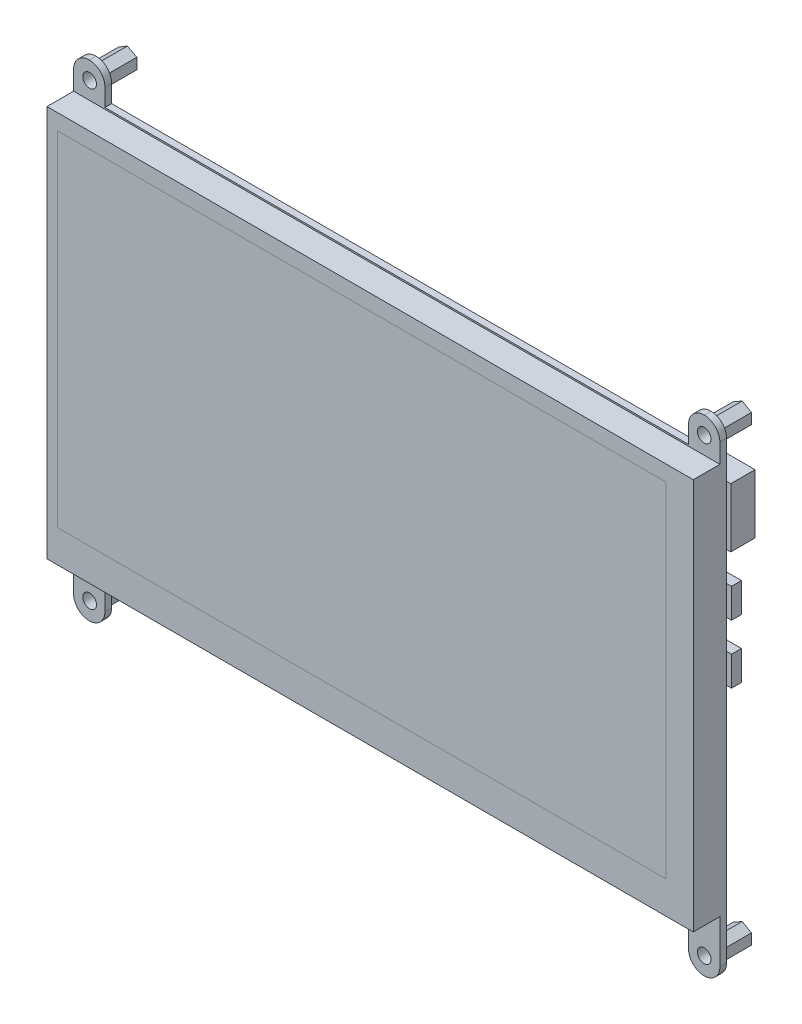
SolidWorks part; units mm, degrees
ref_plane "Plan de face" through (0, 0, 0) normal (0, 0, 1) x (1, 0, 0)
ref_plane "Plan de dessus" through (0, 0, 0) normal (0, 1, 0) x (1, 0, 0)
ref_plane "Plan de droite" through (0, 0, 0) normal (1, 0, 0) x (0, 0, -1)
sketch "Esquisse1" plane through (0, 0, 0) normal (0, 0, 1) x (1, 0, 0)
  line L0 (-74.5, 53.5) -> (74.5, 53.5)
  line L1 (-82.5, 62) -> (-82.5, -62)
  line L2 (-74.5, -53.5) -> (74.5, -53.5)
  line L3 (82.5, 62) -> (82.5, -62)
  line L4 (82.5, -62) -> (74.5, -62)
  line L5 (74.5, -62) -> (74.5, -53.5)
  line L6 (-74.5, -53.5) -> (-74.5, -62)
  line L7 (-74.5, -62) -> (-82.5, -62)
  line L8 (82.5, 62) -> (74.5, 62)
  line L9 (74.5, 62) -> (74.5, 53.5)
  line L10 (-74.5, 53.5) -> (-74.5, 62)
  line L11 (-74.5, 62) -> (-82.5, 62)
  line L12 (78.5, -57.54) -> (78.5, 57.54) construction
  line L13 (78.5, 57.54) -> (-78.4, 57.54) construction
  circle A0 centre (78.5, 57.54) radius 1.75
  circle A1 centre (-78.4, 57.54) radius 1.75
  circle A2 centre (-78.4, -57.54) radius 1.75
  circle A3 centre (78.5, -57.54) radius 1.75
  point P3 (78.5, 0)
  point P21 (78.5, -62)
  point P22 (82.5, 0)
  point P28 (0, 53.5)
  point P29 (-82.5, 0)
  dimension "D1" = 3.5
  dimension "D2" = 165
  dimension "D3" = 107
  dimension "D4" = 8.5
  dimension "D5" = 8
  dimension "D6" = 156.9
  dimension "D7" = 115.08
extrude "Boss.-Extru.1" add sketch "Esquisse1" along normal blind 1.72
fillet "Congé1" radius 4 8 edges at (74.5, -62, 0.86) (82.5, -62, 0.86) (82.5, 62, 0.86) (74.5, 62, 0.86) (-74.5, 62, 0.86) (-82.5, 62, 0.86) (-82.5, -62, 0.86) (-74.5, -62, 0.86)
sketch "Esquisse2" plane through (0, 0, 1.72) normal (0, 0, 1) x (1, 0, 0)
  line L0 (-82.5, 58) -> (-82.5, -58) construction
  line L1 (-82.5, -46.9) -> (82.5, -46.9)
  line L2 (-82.5, -46.9) -> (-82.5, 53.1)
  line L3 (-82.5, 53.1) -> (82.5, 53.1)
  line L4 (82.5, -46.9) -> (82.5, 53.1)
  line L5 (82.5, -58) -> (82.5, 58) construction
  line L6 (74.5, 53.5) -> (-74.5, 53.5) construction
  dimension "D1" = 0.4
  dimension "D2" = 100
extrude "Boss.-Extru.2" add sketch "Esquisse2" along normal blind 6.79
sketch "Esquisse3" plane through (0, 0, 0) normal (0, 0, -1) x (-1, 0, 0)
  line L0 (-74.5, 53.5) -> (74.5, 53.5) construction
  line L1 (-83.57, 33.4) -> (-71.4, 33.4)
  line L2 (-83.57, 33.4) -> (-83.57, 48.5)
  line L3 (-83.57, 48.5) -> (-71.4, 48.5)
  line L4 (-71.4, 33.4) -> (-71.4, 48.5)
  line L5 (-82.5, -58) -> (-82.5, 58) construction
  dimension "D1" = 5
  dimension "D2" = 12.17
  dimension "D3" = 15.1
  dimension "D4" = 1.07
extrude "Boss.-Extru.3" add sketch "Esquisse3" along normal blind 6.19
sketch "Esquisse4" plane through (0, 0, 0) normal (0, 0, -1) x (-1, 0, 0)
  line L0 (-82.5, -58) -> (-82.5, 33.4) construction
  line L1 (-83.75, 18.38) -> (-77.9, 18.38)
  line L2 (-83.75, 18.38) -> (-83.75, 25.9)
  line L3 (-83.75, 25.9) -> (-77.9, 25.9)
  line L4 (-77.9, 18.38) -> (-77.9, 25.9)
  line L5 (-83.75, 3.36) -> (-77.9, 3.36)
  line L6 (-83.75, 3.36) -> (-83.75, 10.88)
  line L7 (-83.75, 10.88) -> (-77.9, 10.88)
  line L8 (-77.9, 3.36) -> (-77.9, 10.88)
  line L9 (-82.5, 33.4) -> (-71.4, 33.4) construction
  dimension "D1" = 7.52
  dimension "D2" = 1.25
  dimension "D3" = 5.85
  dimension "D4" = 7.5
  dimension "D5" = 7.5
extrude "Boss.-Extru.4" add sketch "Esquisse4" along normal blind 2.55
sketch "Esquisse5" plane through (0, 0, 0) normal (0, 0, -1) x (-1, 0, 0)
  line L1 (-78.5, -54.8265) -> (-80.85, -56.1832)
  line L2 (-80.85, -56.1832) -> (-80.85, -58.8968)
  line L3 (-80.85, -58.8968) -> (-78.5, -60.2535)
  line L4 (-78.5, -60.2535) -> (-76.15, -58.8968)
  line L5 (-76.15, -58.8968) -> (-76.15, -56.1832)
  line L6 (-76.15, -56.1832) -> (-78.5, -54.8265)
  line L7 (-78.5, 60.2535) -> (-80.85, 58.8968)
  line L8 (-80.85, 58.8968) -> (-80.85, 56.1832)
  line L9 (-80.85, 56.1832) -> (-78.5, 54.8265)
  line L10 (-78.5, 54.8265) -> (-76.15, 56.1832)
  line L11 (-76.15, 56.1832) -> (-76.15, 58.8968)
  line L12 (-76.15, 58.8968) -> (-78.5, 60.2535)
  line L13 (78.4608, 60.2529) -> (76.081, 58.9491)
  line L14 (76.081, 58.9491) -> (76.0202, 56.2362)
  line L15 (76.0202, 56.2362) -> (78.3392, 54.8271)
  line L16 (78.3392, 54.8271) -> (80.719, 56.1309)
  line L17 (80.719, 56.1309) -> (80.7798, 58.8438)
  line L18 (80.7798, 58.8438) -> (78.4608, 60.2529)
  line L19 (78.4, -54.8265) -> (76.05, -56.1832)
  line L20 (76.05, -56.1832) -> (76.05, -58.8968)
  line L21 (76.05, -58.8968) -> (78.4, -60.2535)
  line L22 (78.4, -60.2535) -> (80.75, -58.8968)
  line L23 (80.75, -58.8968) -> (80.75, -56.1832)
  line L24 (80.75, -56.1832) -> (78.4, -54.8265)
  circle A0 centre (-78.5, -57.54) radius 2.35 construction
  circle A1 centre (-78.5, 57.54) radius 2.35 construction
  circle A2 centre (78.4, 57.54) radius 2.35 construction
  circle A3 centre (78.4, -57.54) radius 2.35 construction
  circle A4 centre (-78.5, 57.54) radius 1.75 construction
  circle A5 centre (-78.5, -57.54) radius 1.75 construction
  circle A6 centre (78.4, -57.54) radius 1.75 construction
  circle A7 centre (78.4, 57.54) radius 1.75 construction
  circle A8 centre (-78.5, 57.54) radius 1.75
  circle A9 centre (-78.5, -57.54) radius 1.75
  circle A10 centre (78.4, -57.54) radius 1.75
  circle A11 centre (78.4, 57.54) radius 1.75
  dimension "D1" = 4.7
extrude "Boss.-Extru.5" add sketch "Esquisse5" along normal blind 8
sketch "Esquisse6" plane through (0, 0, 8.51) normal (0, 0, 1) x (1, 0, 0)
  line L0 (82.5, 53.1) -> (-82.5, 53.1) construction
  line L1 (75.5, 49.1) -> (-79.75, 49.1)
  line L2 (75.5, 49.1) -> (75.5, -38.65)
  line L3 (75.5, -38.65) -> (-79.75, -38.65)
  line L4 (-79.75, 49.1) -> (-79.75, -38.65)
  line L5 (82.5, -46.9) -> (82.5, 53.1) construction
  line L6 (-82.5, 53.1) -> (-82.5, -46.9) construction
  line L7 (-82.5, -46.9) -> (82.5, -46.9) construction
  dimension "D1" = 4
  dimension "D2" = 7
  dimension "D3" = 2.75
  dimension "D4" = 8.25
split line "Ligne de séparation1"
